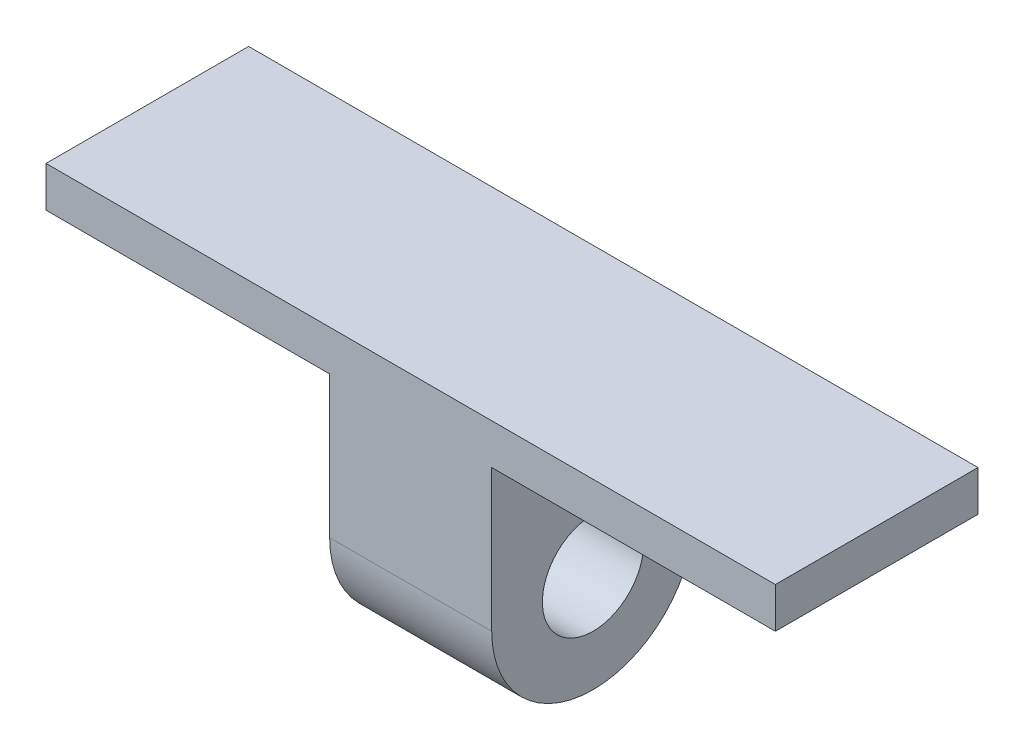
SolidWorks part; units mm, degrees
ref_plane "前视基准面" through (0, 0, 0) normal (0, 0, 1) x (1, 0, 0)
ref_plane "上视基准面" through (0, 0, 0) normal (0, 1, 0) x (1, 0, 0)
ref_plane "右视基准面" through (0, 0, 0) normal (1, 0, 0) x (0, 0, -1)
sketch "草图1" plane through (0, 0, 0) normal (0, 1, 0) x (1, 0, 0)
  line L1 (0, 0) -> (180, 0)
  line L2 (0, 0) -> (0, -50)
  line L3 (0, -50) -> (180, -50)
  line L4 (180, 0) -> (180, -50)
  dimension "D1" = 180
  dimension "D2" = 50
extrude "凸台-拉伸1" add sketch "草图1" along normal blind 10 contours L2 L1 L4 L3
sketch "草图2" plane through (0, 0, 0) normal (0, -1, 0) x (1, 0, 0)
  line L0 (90, 50) -> (90, 0) construction
  line L1 (0, 50) -> (180, 50) construction
  line L2 (0, 0) -> (180, 0) construction
  line L4 (70, 0) -> (110, 0)
  line L5 (70, 0) -> (70, 50)
  line L6 (70, 50) -> (110, 50)
  line L7 (110, 0) -> (110, 50)
  line L8 (70, 0) -> (110, 50) construction
  line L9 (70, 50) -> (110, 0) construction
  point P4 (90, 25)
  dimension "D1" = 40
extrude "凸台-拉伸2" add sketch "草图2" along normal blind 60
fillet "圆角1" radius 25 2 edges at (90, -60, 50) (90, -60, 0)
sketch "草图3" plane through (110, 0, 0) normal (1, 0, 0) x (0, 0, -1)
  line L3 (-50, 0) -> (-50, -35)
  line L4 (0, -35) -> (0, 0)
  line L5 (0, 0) -> (-50, 0)
  line L6 (-50, 0) -> (-50, -35) construction
  line L7 (0, -35) -> (0, 0) construction
  line L8 (0, 0) -> (-50, 0) construction
  circle A0 centre (-25, -35) radius 12.5
  arc A2 (-50, -35) -> (-25, -60) centre (-25, -35) ccw
  arc A3 (-25, -60) -> (0, -35) centre (-25, -35) ccw
  arc A4 (-50, -35) -> (-25, -60) centre (-25, -35) ccw construction
  arc A5 (-25, -60) -> (0, -35) centre (-25, -35) ccw construction
  dimension "D2" = 25
  dimension "D1" = 0
extrude "切除-拉伸2" cut sketch "草图3" against normal through all
